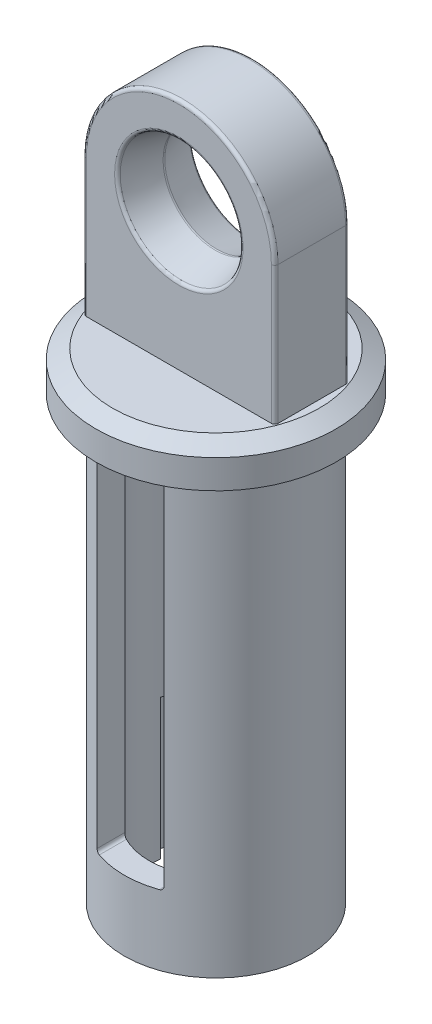
SolidWorks part; units mm, degrees
ref_plane "Alzado" through (0, 0, 0) normal (0, 0, 1) x (1, 0, 0)
ref_plane "Planta" through (0, 0, 0) normal (0, 1, 0) x (1, 0, 0)
ref_plane "Vista lateral" through (0, 0, 0) normal (1, 0, 0) x (0, 0, -1)
sketch "Croquis1" plane through (0, 0, 0) normal (0, 1, 0) x (1, 0, 0)
  circle A0 centre (0, 0) radius 5.5
  dimension "D1" = 11
extrude "Saliente-Extruir1" add sketch "Croquis1" along normal blind 26.5
sketch "Croquis2" plane through (0, 26.5, 0) normal (0, 1, 0) x (1, 0, 0)
  circle A0 centre (0, 0) radius 7.2
  dimension "D1" = 14.4
extrude "Saliente-Extruir2" add sketch "Croquis2" along normal blind 2.3
sketch "Croquis3" plane through (0, 28.8, 0) normal (0, 1, 0) x (1, 0, 0)
  line L0 (-5.75, 0) -> (0, 0) construction
  line L1 (-5.75, 2.225) -> (-5.75, -2.225)
  line L2 (-5.75, -2.225) -> (5.75, -2.225)
  line L3 (5.75, -2.225) -> (5.75, 2.225)
  line L4 (5.75, 2.225) -> (-5.75, 2.225)
  line L5 (0, 0) -> (5.75, 0) construction
  line L6 (0, 2.225) -> (0, 0) construction
  line L7 (0, 0) -> (0, -2.225) construction
  point P4 (0, 0)
  point P8 (-5.75, 0)
  dimension "D1" = 11.5
  dimension "D2" = 4.45
extrude "Saliente-Extruir3" add sketch "Croquis3" along normal blind 14
sketch "Croquis4" plane through (0, 0, 2.225) normal (0, 0, 1) x (1, 0, 0)
  line L0 (-5.75, 42.8) -> (5.75, 42.8)
  line L1 (5.75, 42.8) -> (5.75, 37.05)
  line L3 (-5.75, 42.8) -> (-5.75, 37.05)
  arc A1 (5.75, 37.05) -> (-5.75, 37.05) centre (0, 37.05) ccw
  line M6 (5.75, 28.8) -> (5.75, 42.8)
  line M7 (5.75, 42.8) -> (-5.75, 42.8)
  line M8 (-5.75, 42.8) -> (-5.75, 28.8)
extrude "Cortar-Extruir1" cut sketch "Croquis4" against normal blind 13.37 contours A1 M6 M7 | A1 L0 M8 | L0 L1 A1 L3 region at (4.4656, 41.5156, 2.225) region at (-4.4656, 41.5156, 2.225)
sketch "Croquis6" plane through (0, 0, 0) normal (0, -1, 0) x (1, 0, 0)
  circle A0 centre (0, 0) radius 4
  dimension "D1" = 8
extrude "Cortar-Extruir2" cut sketch "Croquis6" against normal up to surface (26.5 mm away) up to face at (0, 26.5, 5.5)
sketch "Croquis7" plane through (0, 0, 2.225) normal (0, 0, 1) x (1, 0, 0)
  circle A0 centre (0, 37.05) radius 2.8
  dimension "D1" = 5.6
extrude "Cortar-Extruir3" cut sketch "Croquis7" against normal blind 26.37
chamfer "Chaflán1" distance 0.9 angle 75 1 edges at (2.8, 37.05, 2.225) first distance on face at (2.8, 37.05, 2.225)
chamfer "Chaflán2" distance 0.9 angle 75 1 edges at (2.8, 37.05, -2.225) first distance on face at (2.8, 37.05, -2.225)
fillet "Redondeo1" radius 0.2 6 edges at (5.75, 32.925, 2.225) (0, 42.8, 2.225) (-5.75, 32.925, 2.225) (5.75, 32.925, -2.225) (-5.75, 32.925, -2.225) (0, 42.8, -2.225)
fillet "Redondeo2" radius 0.2 3 edges at (-3.7, 37.05, 2.225) (-3.1038, 37.05, 0) (3.7, 37.05, -2.225)
ref_plane "Plano2" through (0, 0, 12.225) normal (0, 0, 1) x (1, 0, 0)
sketch "Croquis11" plane through (0, 0, 12.225) normal (0, 0, 1) x (1, 0, 0)
  line L0 (-5.5, 26.5) -> (5.5, 26.5) construction
  line L1 (-2, 26.5) -> (2, 26.5)
  line L2 (-2, 26.5) -> (-2, 4.2)
  line L3 (-2, 4.2) -> (2, 4.2)
  line L4 (2, 26.5) -> (2, 4.2)
  line L5 (0, 4.2) -> (0, 0) construction
  dimension "D1" = 22.3
  dimension "D2" = 4
extrude "Cortar-Extruir4" cut sketch "Croquis11" against normal through all
sketch "Croquis13" plane through (0, 0, 0) normal (0, -1, 0) x (1, 0, 0)
  line L0 (-2, 5.1235) -> (-2, -5.1235) construction
  line L1 (2, 5.1235) -> (2, -5.1235) construction
  line L2 (-2, -4.1979) -> (4.5201, 1.0916)
  line L3 (2, 4.1979) -> (-4.5201, -1.0916)
  line L4 (-1.26, 1.5532) -> (1.26, -1.5532) construction
  line L5 (-2, -4.1979) -> (2, -4.1979) construction
  arc A0 (-4.5201, -1.0916) -> (-2, -4.1979) centre (0, 0) ccw
  arc A1 (4.5201, 1.0916) -> (2, 4.1979) centre (0, 0) ccw
  point P17 (0, 0)
  dimension "D1" = 9.3
extrude "Cortar-Extruir5" cut sketch "Croquis13" against normal blind 8.4
fillet "Redondeo3" radius 0.2 8 edges at (2, 4.2, 4.6607) (-2, 4.2, 4.2938) (2, 26.5, 4.2938) (-2, 26.5, 4.2938) (-2, 26.5, -4.2938) (2, 26.5, -4.2938) (2, 4.2, -4.2938) (-2, 4.2, -4.6607)
chamfer "Chaflán3" distance 1 angle 30 1 edges at (0, 28.8, 7.2) first distance on face at (0, 28.8, 0)
